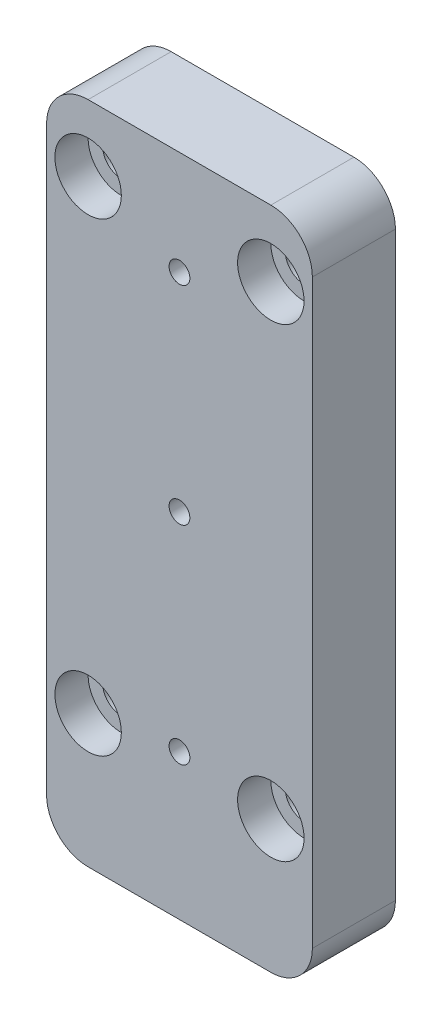
SolidWorks part; units mm, degrees
ref_plane "Front" through (0, 0, 0) normal (0, 0, 1) x (1, 0, 0)
ref_plane "Top" through (0, 0, 0) normal (0, 1, 0) x (1, 0, 0)
ref_plane "Right" through (0, 0, 0) normal (1, 0, 0) x (0, 0, -1)
sketch "Esquisse1" plane through (0, 0, 0) normal (0, 0, 1) x (1, 0, 0)
  line L1 (0, 0) -> (32, 0)
  line L2 (0, 0) -> (0, 80)
  line L3 (0, 80) -> (32, 80)
  line L4 (32, 0) -> (32, 80)
  dimension "D1" = 32
  dimension "D2" = 80
extrude "Boss.-Extru.1" add sketch "Esquisse1" along normal blind 10
sketch "Esquisse2" plane through (0, 0, 10) normal (0, 0, 1) x (1, 0, 0)
  line L0 (16, 0) -> (16, 80) construction
  line L1 (0, 0) -> (32, 0) construction
  line L2 (32, 80) -> (0, 80) construction
  circle A0 centre (16, 17.5) radius 1.25
  circle A1 centre (16, 42.5) radius 1.25
  circle A2 centre (16, 67.5) radius 1.25
  circle A3 centre (16, 92.5) radius 1.25
  circle A4 centre (16, 117.5) radius 1.25
  circle A5 centre (16, 142.5) radius 1.25
  circle A6 centre (16, 167.5) radius 1.25
  circle A7 centre (16, 192.5) radius 1.25
  dimension "D1" = 17.5
  dimension "D2" = 2.5
  dimension "D4" = 25
  dimension "D3" = 8
extrude "Enlèv. mat.-Extru.1" cut sketch "Esquisse2" against normal through all both and the other way through all
sketch "Esquisse3" plane through (0, 0, 10) normal (0, 0, 1) x (1, 0, 0)
  line L0 (16, 0) -> (16, 80) construction
  line L1 (0, 0) -> (32, 0) construction
  line L2 (32, 80) -> (0, 80) construction
  line L3 (0, 44) -> (32, 44) construction
  line L5 (32, 0) -> (32, 80) construction
  line L6 (0, 80) -> (0, 0) construction
  circle A0 centre (5, 16) radius 2.25
  circle A1 centre (27, 16) radius 2.25
  circle A2 centre (27, 72) radius 2.25
  circle A3 centre (5, 72) radius 2.25
  point P12 (0, 45.8106)
  point P20 (0, 0)
  dimension "D1" = 22
  dimension "D2" = 16
  dimension "D3" = 4.5
  dimension "D4" = 56
extrude "Enlèv. mat.-Extru.2" cut sketch "Esquisse3" against normal through all both and the other way through all
sketch "Esquisse4" plane through (0, 0, 10) normal (0, 0, 1) x (1, 0, 0)
  circle A0 centre (5, 16) radius 4
  circle A1 centre (27, 16) radius 4
  circle A2 centre (5, 72) radius 4
  circle A3 centre (27, 72) radius 4
  dimension "D1" = 8
extrude "Enlèv. mat.-Extru.3" cut sketch "Esquisse4" against normal blind 4
fillet "Congé1" radius 5 4 edges at (0, 80, 5) (32, 80, 5) (32, 0, 5) (0, 0, 5)
